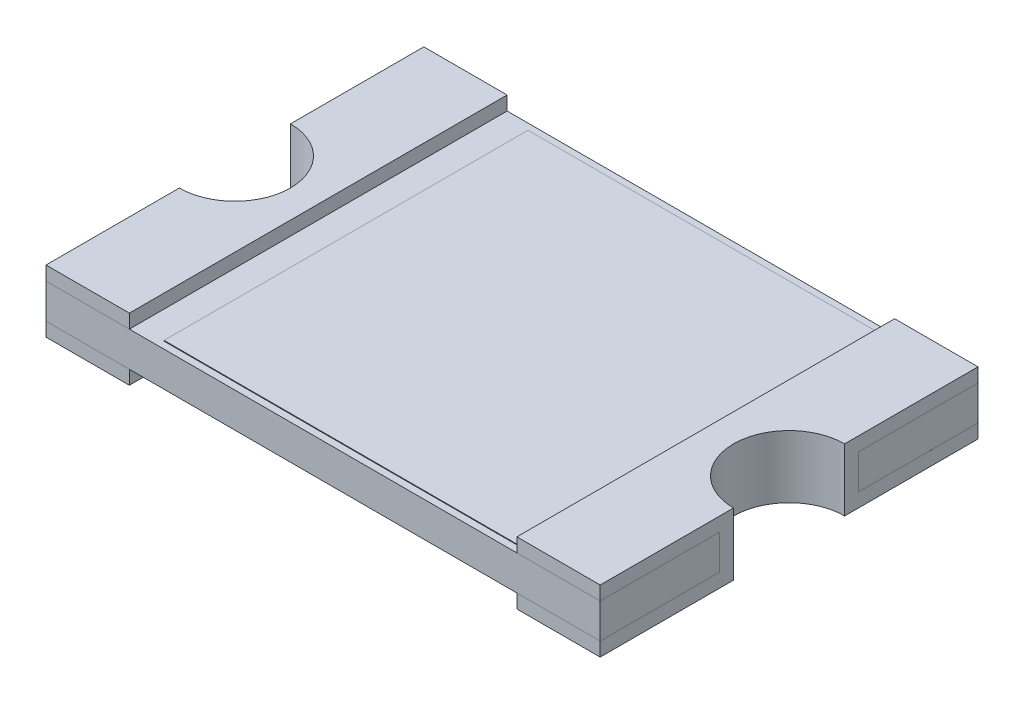
SolidWorks part; units mm, degrees
material "1060 Alloy"
ref_plane "Front Plane" through (0, 0, 0) normal (0, 0, 1) x (1, 0, 0)
ref_plane "Top Plane" through (0, 0, 0) normal (0, 1, 0) x (1, 0, 0)
ref_plane "Right Plane" through (0, 0, 0) normal (1, 0, 0) x (0, 0, -1)
sketch "Sketch2" plane through (0, 0, 0) normal (0, 1, 0) x (1, 0, 0)
  line L0 (-2.79, -2.72) -> (-2.79, 2.72) construction
  line L1 (-3.99, 2.72) -> (3.99, 2.72) construction
  line L2 (-3.99, 2.72) -> (-3.99, -2.72) construction
  line L3 (-3.99, -2.72) -> (3.99, -2.72) construction
  line L4 (3.99, 2.72) -> (3.99, -2.72) construction
  line L5 (2.79, 2.72) -> (2.79, -2.72) construction
  line L6 (-3.99, 0) -> (-2.79, 0) construction
  line L7 (3.99, 0) -> (2.79, 0) construction
  line L8 (-2.39, 2.62) -> (-2.39, -2.62) construction
  line L9 (-2.39, 2.62) -> (2.79, 2.62) construction
  line L10 (-2.39, -2.62) -> (2.79, -2.62) construction
  arc A0 (-3.99, 0.8) -> (-3.99, -0.8) centre (-3.99, 0) cw construction
  arc A1 (3.99, 0.8) -> (3.99, -0.8) centre (3.99, 0) ccw construction
  arc A2 (3.99, 1) -> (3.99, -1) centre (3.99, 0) ccw construction
  arc A3 (-3.99, 1) -> (-3.99, -1) centre (-3.99, 0) cw construction
  point P4 (-3.99, 0)
  point P6 (0, -2.72)
  point P17 (3.99, 0)
  point P35 (-2.39, 0)
  dimension "D1" = 0.8
  dimension "D2" = 1.2
  dimension "D3" = 7.98
  dimension "D4" = 5.44
  dimension "D5" = 0.4
  dimension "D6" = 0.2
  dimension "D7" = 0.1
sketch "Sketch3" plane through (0, 0, 0) normal (0, 0, 1) x (1, 0, 0)
  line L0 (-3.99, 0.7) -> (3.99, 0.7) construction
  line L1 (-3.99, 0.9) -> (3.99, 0.9) construction
  line L2 (-3.99, 0.9) -> (-3.99, 0) construction
  line L3 (-3.99, 0) -> (3.99, 0) construction
  line L4 (3.99, 0.9) -> (3.99, 0) construction
  line L5 (-3.99, 0.2) -> (3.99, 0.2) construction
  line L6 (0, 0.7) -> (0, 0.2) construction
  line L7 (0, 0.2) -> (0, 0) construction
  line L8 (0, 0.7) -> (0, 0.9) construction
  line L9 (-2.79, 0.9) -> (-2.79, 0) construction
  line L10 (2.79, 0.9) -> (2.79, 0) construction
  line L11 (-2.39, 0.7) -> (-2.39, 0.71) construction
  line L12 (-2.39, 0.71) -> (2.79, 0.71) construction
  point P7 (0, 0)
  point P20 (0, 0)
  dimension "D1" = 0.9
  dimension "D2" = 0.5
  dimension "D3" = 0.01
sketch "Sketch4" plane through (0, 0, 0) normal (0, 0, 1) x (1, 0, 0)
  line L1 (-3.99, 0.7) -> (3.99, 0.7)
  line L2 (-3.99, 0.7) -> (-3.99, 0.2)
  line L3 (-3.99, 0.2) -> (3.99, 0.2)
  line L4 (3.99, 0.7) -> (3.99, 0.2)
extrude "Boss-Extrude1" add sketch "Sketch4" against normal up to vertex (2.72 mm away) from vertex up to point (-3.99, 0, -2.72) starting at point (-3.99, 0, 2.72)
sketch "Sketch7" plane through (0, 0, 0) normal (0, 0, 1) x (1, 0, 0)
  line L1 (-3.99, 0.7) -> (-2.79, 0.7)
  line L2 (-3.99, 0.7) -> (-3.99, 0.9)
  line L3 (-3.99, 0.9) -> (-2.79, 0.9)
  line L4 (-2.79, 0.7) -> (-2.79, 0.9)
  line L5 (-3.99, 0.2) -> (-2.79, 0.2)
  line L6 (-3.99, 0.2) -> (-3.99, 0)
  line L7 (-3.99, 0) -> (-2.79, 0)
  line L8 (-2.79, 0.2) -> (-2.79, 0)
  line L9 (3.99, 0.7) -> (2.79, 0.7)
  line L10 (3.99, 0.7) -> (3.99, 0.9)
  line L11 (3.99, 0.9) -> (2.79, 0.9)
  line L12 (2.79, 0.7) -> (2.79, 0.9)
  line L13 (3.99, 0.2) -> (2.79, 0.2)
  line L14 (3.99, 0.2) -> (3.99, 0)
  line L15 (3.99, 0) -> (2.79, 0)
  line L16 (2.79, 0.2) -> (2.79, 0)
extrude "Boss-Extrude2" add sketch "Sketch7" against normal up to vertex (2.72 mm away) from vertex separate body up to point (-3.99, 0, -2.72) starting at point (-3.99, 0, 2.72)
sketch "Sketch6" plane through (0, 0, 0) normal (0, 1, 0) x (1, 0, 0)
  line L4 (3.99, 2.72) -> (3.99, -2.72) construction
  line L5 (-3.99, 2.72) -> (-3.99, -2.72) construction
  line L6 (3.99, 1) -> (3.99, -1)
  line L7 (-3.99, 1) -> (-3.99, -1)
  arc A4 (3.99, 1) -> (3.99, -1) centre (3.99, 0) ccw construction
  arc A5 (-3.99, -1) -> (-3.99, 1) centre (-3.99, 0) ccw construction
  arc A6 (3.99, 1) -> (3.99, -1) centre (3.99, 0) ccw
  arc A7 (-3.99, -1) -> (-3.99, 1) centre (-3.99, 0) ccw
extrude "Cut-Extrude1" cut sketch "Sketch6" along normal through all
sketch "Sketch9" plane through (0, 0, 0) normal (0, 1, 0) x (1, 0, 0)
  line L0 (3.99, 2.72) -> (3.99, -2.72) construction
  line L1 (-3.99, 2.72) -> (-3.99, -2.72) construction
  line L2 (3.99, 1) -> (3.99, 0.8)
  line L3 (-3.99, 1) -> (-3.99, 0.8)
  line L4 (-3.99, -0.8) -> (-3.99, -1)
  line L5 (3.99, -0.8) -> (3.99, -1)
  arc A0 (3.99, 1) -> (3.99, -1) centre (3.99, 0) ccw construction
  arc A1 (3.99, 0.8) -> (3.99, -0.8) centre (3.99, 0) ccw construction
  arc A2 (-3.99, -1) -> (-3.99, 1) centre (-3.99, 0) ccw construction
  arc A3 (-3.99, -0.8) -> (-3.99, 0.8) centre (-3.99, 0) ccw construction
  arc A4 (3.99, 1) -> (3.99, -1) centre (3.99, 0) ccw
  arc A5 (3.99, 0.8) -> (3.99, -0.8) centre (3.99, 0) ccw
  arc A6 (-3.99, -1) -> (-3.99, 1) centre (-3.99, 0) ccw
  arc A7 (-3.99, -0.8) -> (-3.99, 0.8) centre (-3.99, 0) ccw
extrude "Boss-Extrude3" add sketch "Sketch9" along normal up to vertex (0.9 mm away) from vertex up to point (-3.99, 0.9, 0) starting at point (-3.99, 0, 0)
sketch "Sketch11" plane through (0, 0, 0) normal (0, 1, 0) x (1, 0, 0)
  line L1 (-2.39, 2.62) -> (2.79, 2.62)
  line L2 (-2.39, 2.62) -> (-2.39, -2.62)
  line L3 (-2.39, -2.62) -> (2.79, -2.62)
  line L4 (2.79, 2.62) -> (2.79, -2.62)
extrude "Boss-Extrude4" add sketch "Sketch11" along normal up to vertex (0.71 mm away) from vertex separate body up to point (-2.39, 0.71, 0) starting at point (-2.39, 0.7, 0)
